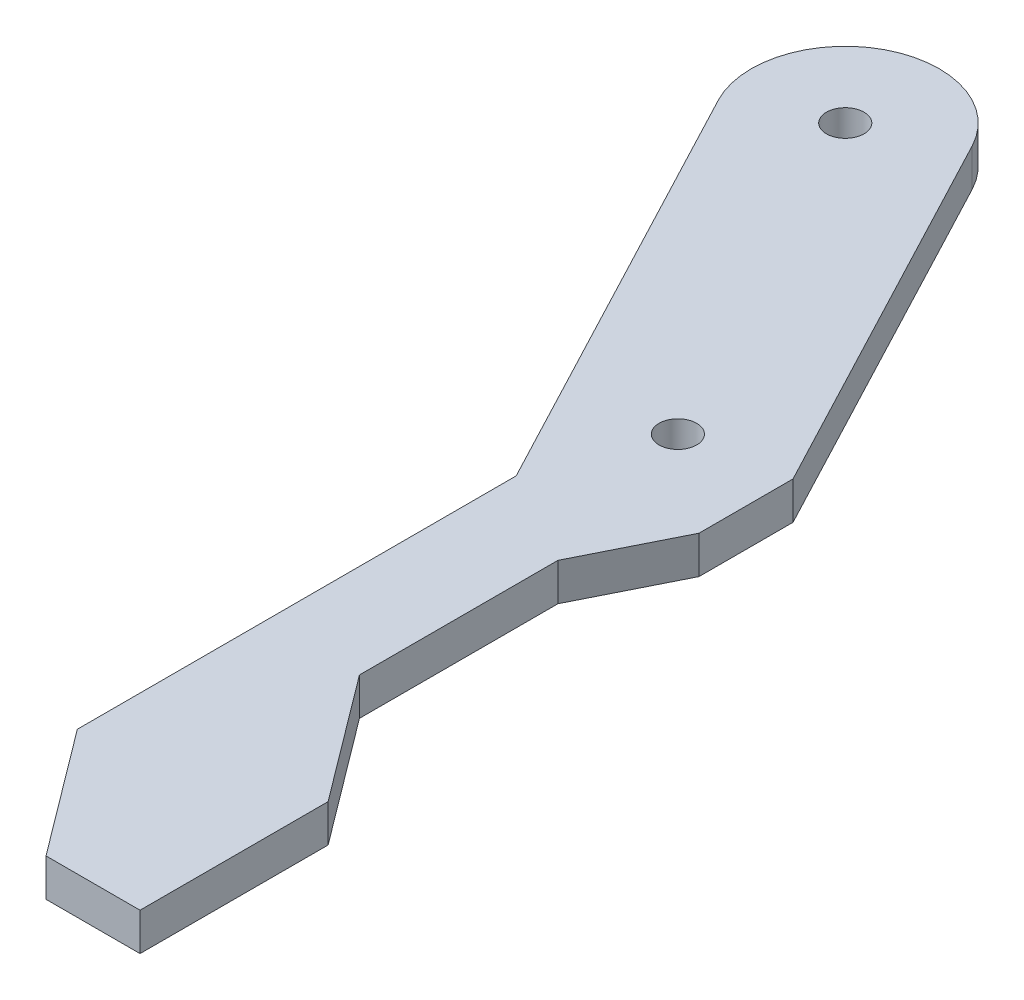
SolidWorks part; units mm, degrees
ref_plane "Alzado" through (0, 0, 0) normal (0, 0, 1) x (1, 0, 0)
ref_plane "Planta" through (0, 0, 0) normal (0, 1, 0) x (1, 0, 0)
ref_plane "Vista lateral" through (0, 0, 0) normal (1, 0, 0) x (0, 0, -1)
sketch "Croquis1" plane through (0, 0, 0) normal (0, 1, 0) x (1, 0, 0)
  line L0 (2.495, 24.5553) -> (12.3715, 5.7778) construction
  line L1 (-1.9302, 22.2277) -> (9.995, -0.4447)
  line L2 (-2.505, 24.5553) -> (-2.505, -39.1191) construction
  line L3 (6.9202, 26.8828) -> (17.495, 6.7778)
  line L4 (17.495, 6.7778) -> (17.495, 1.7778)
  line L5 (17.495, 1.7778) -> (17.495, -39.1191) construction
  line L6 (17.495, 1.7778) -> (14.995, -3.2222)
  line L7 (9.995, -0.4447) -> (9.995, -23.7781)
  line L8 (14.995, -13.7781) -> (14.995, -36.0632) construction
  line L9 (2.495, 29.5553) -> (58.6141, 29.5553) construction
  line L10 (9.995, -0.4447) -> (29.249, -0.4447) construction
  line L11 (14.995, -3.2222) -> (17.945, -3.2222) construction
  line L12 (19.498, -19.782) -> (11.498, -25.782) construction
  line L13 (17.495, 6.7778) -> (9.6002, 6.7778) construction
  line L14 (4.599, 9.8142) -> (13.4495, 14.4693) construction
  line L17 (14.995, -3.2222) -> (14.995, -13.7781)
  line L18 (14.995, -13.7781) -> (19.995, -20.4447)
  line L19 (9.995, -23.7781) -> (14.995, -30.4447)
  line L20 (14.995, -30.4447) -> (19.995, -30.4447)
  line L21 (19.995, -30.4447) -> (19.995, -20.4447)
  line L23 (19.995, -20.4447) -> (24.9172, -20.4447) construction
  line L24 (19.995, -30.4447) -> (41.1083, -30.4447) construction
  line L25 (9.995, -23.7781) -> (9.995, -40.4419) construction
  line L26 (19.995, -30.4447) -> (19.995, -40.4419) construction
  circle A0 centre (2.495, 24.5553) radius 1
  arc A1 (6.9202, 26.8828) -> (-1.9302, 22.2277) centre (2.495, 24.5553) ccw
  circle A2 centre (12.3715, 5.7778) radius 1
  dimension "D12" = 2
  dimension "D1" = 5
  dimension "D2" = 20
  dimension "D3" = 5
  dimension "D4" = 10
  dimension "D5" = 30
  dimension "D6" = 10
  dimension "D7" = 5
  dimension "D8" = 10
  dimension "D9" = 10
  dimension "D10" = 5
  dimension "D11" = 60
extrude "Saliente-Extruir1" add sketch "Croquis1" along normal blind 2
